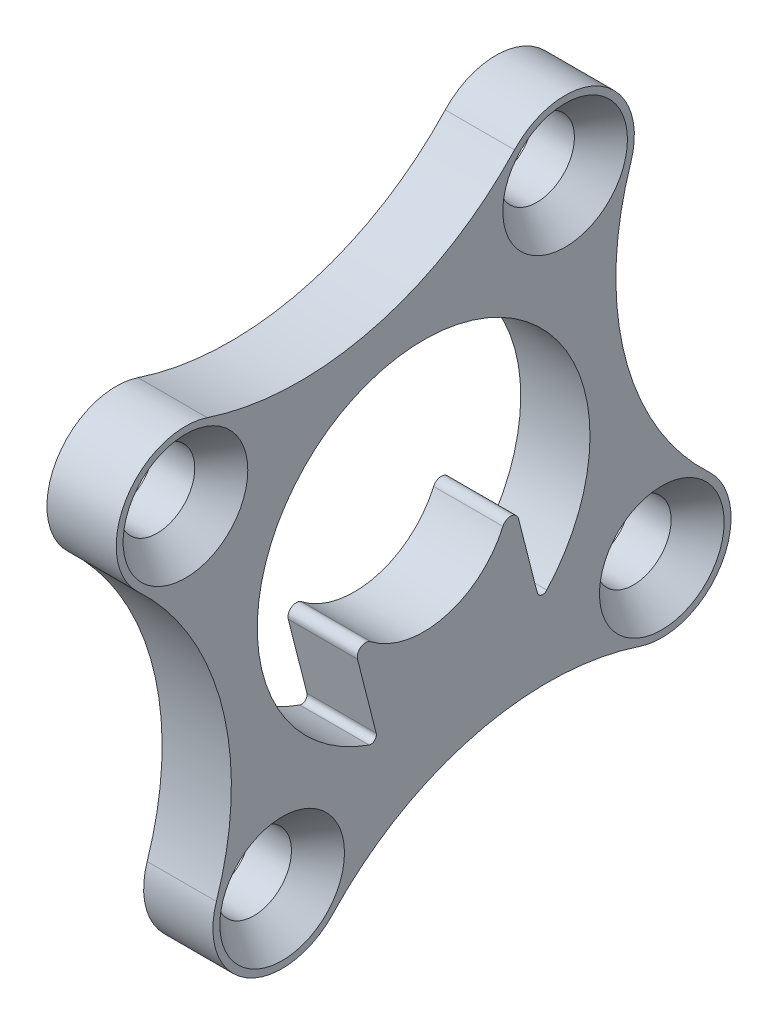
SolidWorks part; units mm, degrees
material "6061-T6 (SS)"
ref_plane "Front Plane" through (0, 0, 0) normal (0, 0, 1) x (1, 0, 0)
ref_plane "Top Plane" through (0, 0, 0) normal (0, 1, 0) x (1, 0, 0)
ref_plane "Right Plane" through (0, 0, 0) normal (1, 0, 0) x (0, 0, -1)
sketch "Sketch1" plane through (-48.665, 0, 0) normal (-1, 0, 0) x (0, 0, 1)
  line L0 (-5.2105, -5.0212) -> (-4.3527, -1.6531)
  line L1 (-5.6279, -6.6601) -> (-5.1728, -4.8731) construction
  line L2 (3.0316, -3.5338) -> (2.1738, -6.9019)
  line L3 (1.7563, -8.5408) -> (2.9869, -3.7095) construction
  line L5 (-5.1728, -4.8731) -> (-3.9664, -0.1365) construction
  line L6 (-6.486, 10.9189) -> (6.486, -10.9189) construction
  line L7 (10.9189, 6.486) -> (-10.9189, -6.486) construction
  arc A0 (-4.3527, -1.6531) -> (-3.6345, -1.5941) centre (-3.9834, -1.7471) cw
  arc A1 (-3.6345, -1.5941) -> (2.4292, -3.1385) centre (0, 0) ccw
  arc A2 (2.4292, -3.1385) -> (3.0316, -3.5338) centre (2.6624, -3.4398) cw
  circle A3 centre (0, 0) radius 3.9687 construction
  circle A4 centre (0, 0) radius 3.9687 construction
  arc A5 (-5.2105, -5.0212) -> (-5.6446, -5.1293) centre (-5.4566, -4.9585) cw
  arc A8 (-5.6446, -5.1293) -> (2.5033, -7.2045) centre (0, 0) cw
  arc A9 (2.5033, -7.2045) -> (2.1738, -6.9019) centre (2.4199, -6.9646) cw
  circle A10 centre (0, 0) radius 15.875
  arc A11 (2.5438, -7.0554) -> (-5.6089, -4.979) centre (0, 0) ccw construction
  circle A12 centre (-10.9189, -6.486) radius 3.175 construction
  circle A13 centre (-10.9189, -6.486) radius 2.6924 construction
  circle A14 centre (0, 0) radius 9.525 construction
  dimension "D1" = 0.381
  dimension "D2" = 0.254
  dimension "D3" = 25.4
  dimension "D4" = 0.127
  dimension "D6" = 5.3848
  dimension "D7" = 19.05
  dimension "D5" = 45
extrude "Boss-Extrude1" add sketch "Sketch1" against normal blind 3.175
sketch "Sketch2" plane through (-48.665, 0, 0) normal (-1, 0, 0) x (0, 0, 1)
  line L0 (10.9189, 6.486) -> (-10.9189, -6.486) construction
  line L1 (-5.2105, -5.0212) -> (-4.3527, -1.6531) construction
  line L2 (-9.2303, 2.3509) -> (-15.3839, 3.9182)
  arc A0 (-13.6486, -8.1075) -> (-15.3839, 3.9182) centre (0, 0) cw
  circle A1 centre (0, 0) radius 15.875 construction
  circle A3 centre (0, 0) radius 9.525 construction
  arc A5 (-13.0867, -4.1663) -> (-13.6486, -8.1075) centre (-10.9189, -6.486) ccw
  circle A6 centre (-10.9189, -6.486) radius 3.175 construction
  arc A7 (-13.0867, -4.1663) -> (-9.2303, 2.3509) centre (-22.284, 5.6756) ccw
extrude "Cut-Extrude1" cut sketch "Sketch2" against normal through all
mirror "Mirror1" about plane through (-45.49, 2.3509, -9.2303) normal (0, 0.9691, 0.2468) of "Cut-Extrude1"
pattern_circular "CirPattern2" count 4 over 360 about axis through (-48.665, 0, 0) along (-1, 0, 0) of "Cut-Extrude1", "Mirror1"
hole_wizard "CSK for #4 Flat Head Machine Screw1" positions "Sketch3" profile "Sketch4" countersink size "#4" standard "ANSI Inch" end condition up to next
sketch "Sketch3" plane through (-45.49, 0, 0) normal (1, 0, 0) x (0, 0, -1)
  point P0 (-6.486, -10.9189)
  point P3 (-6.486, -10.9189)
  point P6 (-6.486, -10.9189)
  point P9 (-6.486, -10.9189)
  point P13 (10.9189, -6.486)
  point P16 (6.486, 10.9189)
  point P19 (-10.9189, 6.486)
sketch "Sketch4" plane through (-45.49, -10.9189, 6.486) normal (0, 1, 0) x (0, 0, -1)
  line L0 (0, 0) -> (0, 3.175)
  line L1 (0, 3.175) -> (1.7272, 3.175)
  line L2 (1.7272, 3.175) -> (1.7272, 1.3003)
  line L3 (1.7272, 1.3003) -> (2.8575, 0)
  line L5 (2.8575, 0) -> (0, 0)
  line L6 (-1.7272, 1.3003) -> (-2.8575, 0) construction
  line L11 (0, -6.35) -> (0, 107.95) construction
  dimension "Thru Hole Dia." = 3.4544
  dimension "Thru Hole Depth" = 3.175
  dimension "Near C'Sink Dia." = 5.715
  dimension "Near C'Sink Angle" = 82
